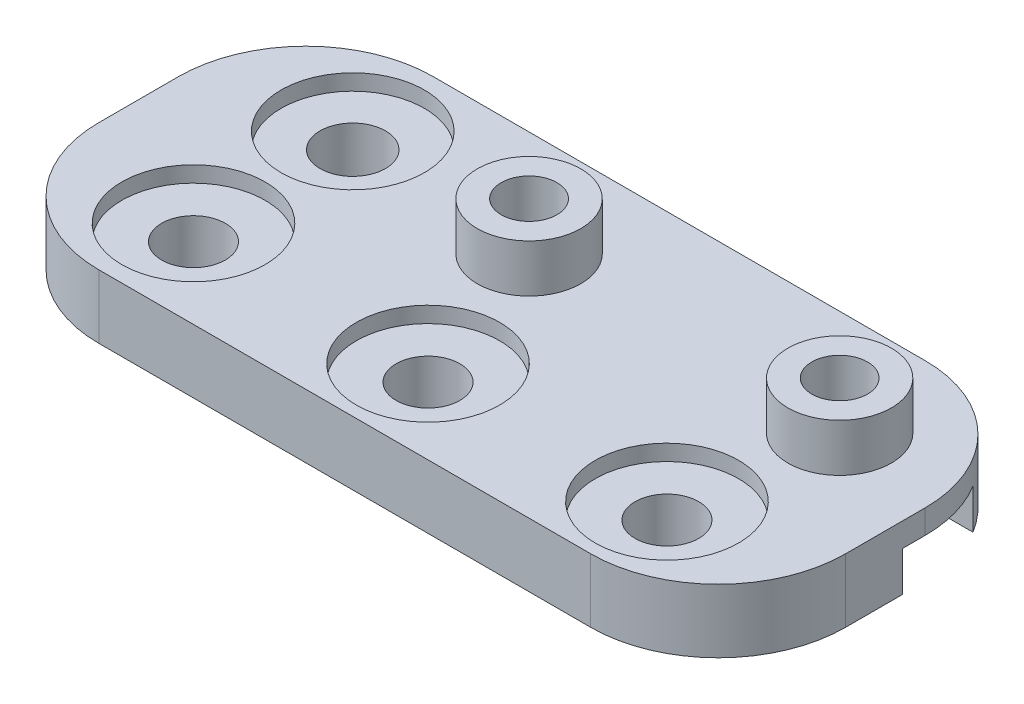
SolidWorks part; units mm, degrees
ref_plane "Front Plane" through (0, 0, 0) normal (0, 0, 1) x (1, 0, 0)
ref_plane "Top Plane" through (0, 0, 0) normal (0, 1, 0) x (1, 0, 0)
ref_plane "Right Plane" through (0, 0, 0) normal (1, 0, 0) x (0, 0, -1)
sketch "Sketch1" plane through (0, 0, 0) normal (0, 1, 0) x (1, 0, 0)
  line L0 (-17.8, 8) -> (-17.8, -8) construction
  line L1 (-20, 8) -> (20, 8)
  line L2 (-20, 8) -> (-20, -8)
  line L3 (-20, -8) -> (20, -8)
  line L4 (20, 8) -> (20, -8)
  line L5 (-20, 5.2) -> (20, 5.2) construction
  circle A0 centre (-17.8, 5.2) radius 1.75
  circle A1 centre (-17.8, -5.8) radius 1.75
  circle A2 centre (-2.8, 5.2) radius 1.75
  circle A3 centre (16.7, 5.2) radius 1.75
  point P4 (-20, 0)
  point P6 (0, 8)
  dimension "D5" = 3.5
  dimension "D1" = 16
  dimension "D2" = 40
  dimension "D3" = 2.2
  dimension "D4" = 2.8
  dimension "D6" = 15
  dimension "D7" = 19.5
  dimension "D8" = 11
sketch "Sketch2" plane through (0, 0, 0) normal (0, 1, 0) x (1, 0, 0)
  line L0 (0, 11.8295) -> (0, -25.9438) construction
  line L1 (-23.4419, 11.8295) -> (23.4419, 11.8295)
  line L2 (-23.4419, 11.8295) -> (-23.4419, -25.9438)
  line L3 (-23.4419, -25.9438) -> (23.4419, -25.9438)
  line L4 (23.4419, 11.8295) -> (23.4419, -25.9438)
  line L5 (-23.4419, -9.1705) -> (23.4419, -9.1705)
  circle A1 centre (-2.8, 5.2) radius 3.25
  circle A2 centre (16.7, 5.2) radius 3.25
  circle A5 centre (0, -18.9438) radius 2
  circle A6 centre (0, -3.9438) radius 2
  circle A7 centre (-14.9975, -3.6705) radius 2
  circle A8 centre (-14.9975, 6.3295) radius 2.0541
  point P18 (0, 11.8295)
  dimension "D1" = 15
  dimension "D2" = 4
  dimension "D3" = 4
  dimension "D6" = 4
  dimension "D4" = 22
  dimension "D5" = 15
  dimension "D7" = 10
  dimension "D8" = 5.5
  dimension "D9" = 5.5
extrude "Boss-Extrude2" add sketch "Sketch2" along normal blind 4 contours L1 L0 A1 A6 L5 L4 A2 | L0 L1 L2 L5 A6 A1 A8 A7 region at (11.5321, 0, -1.1099) region at (-12.3466, 0, -1.1078)
extrude "Boss-Extrude3" add sketch "Sketch2<2>" along normal blind 7 contours L0 A1 | A2 | A1 L0 region at (0.1811, 0, -5.2) region at (-2.8931, 0, -5.2) region at (16.7, 0, -5.2)
sketch "Sketch2<2>" plane through (0, 0, 0) normal (0, 1, 0) x (1, 0, 0) same geometry as "Sketch2"
extrude "Cut-Extrude1" cut sketch "Sketch1" along normal up to next contours A2 | A3 region at (-2.8, 0, -5.2)
hole_wizard "Hole1" positions "Sketch3" profile "Sketch5" legacy end condition up to next
sketch "Sketch3" plane through (0, 4, 0) normal (0, 1, 0) x (1, 0, 0)
  line L0 (15, -3.9438) -> (0, -3.9438) construction
  point P0 (0, -3.9438)
  point P6 (15, -3.9438)
  point P13 (-14.9975, -3.6705)
  point P16 (-14.9975, 6.3295)
  point P20 (0, 0)
sketch "Sketch5" plane through (0, 4, 3.9438) normal (1, 0, 0) x (0, 0, 1)
  line L0 (0, 0) -> (0, 4)
  line L1 (0, 4) -> (2, 4)
  line L2 (2, 4) -> (2, 1)
  line L3 (2, 1) -> (4.5, 1)
  line L4 (4.5, 1) -> (4.5, 0)
  line L5 (4.5, 0) -> (0, 0)
  line L6 (0, 110) -> (0, -10) construction
  dimension "Diameter" = 4
  dimension "Depth" = 4
  dimension "C-Bore Diameter" = 9
  dimension "C-Bore Depth" = 1
fillet "Fillet1" radius 8 4 edges at (-23.4419, 2, -11.8295) (23.4419, 2, -11.8295) (-23.4419, 2, 9.1705) (23.4419, 2, 9.1705)
sketch "Sketch6" plane through (0, 0, 0) normal (0, -1, 0) x (1, 0, 0)
  line L0 (-6.0332, -8) -> (-6.0332, -2.4)
  line L1 (13.4668, -5.2) -> (15.0834, -8)
  line L2 (15.0834, -8) -> (18.3166, -8)
  line L3 (18.3166, -8) -> (19.9332, -5.2)
  line L4 (19.9332, -5.2) -> (18.3166, -2.4)
  line L5 (18.3166, -2.4) -> (15.0834, -2.4)
  line L6 (15.0834, -2.4) -> (13.4668, -5.2)
  line L7 (0.4332, -5.2) -> (-1.1834, -2.4)
  line L8 (-1.1834, -2.4) -> (-4.4166, -2.4)
  line L9 (-4.4166, -2.4) -> (-6.0332, -5.2)
  line L10 (-6.0332, -5.2) -> (-4.4166, -8)
  line L11 (-4.4166, -8) -> (-1.1834, -8)
  line L12 (-1.1834, -8) -> (0.4332, -5.2)
  line L13 (-6.0332, -2.4) -> (29.8793, -2.4)
  line L14 (29.8793, -2.4) -> (29.8793, -8)
  line L15 (29.8793, -8) -> (-6.0332, -8)
  circle A0 centre (16.7, -5.2) radius 2.8 construction
  circle A1 centre (-2.8, -5.2) radius 2.8 construction
  dimension "D1" = 5.6
extrude "Cut-Extrude2" cut sketch "Sketch6" against normal blind 2.5 contours L15 L13 L4 L3 | L5 L6 L1 L2 L3 L4 | L15 L1 L6 L13 L7 L12 | L11 L12 L7 L8 L9 L10 | L13 L0 L9 | L15 L10 L0 region at (-5.4943, 0, -7.0667) region at (-5.4943, 0, -3.3333) region at (-2.8, 0, -5.2) region at (6.95, 0, -5.2) region at (16.7, 0, -5.2) region at (24.4919, 0, -5.2)
